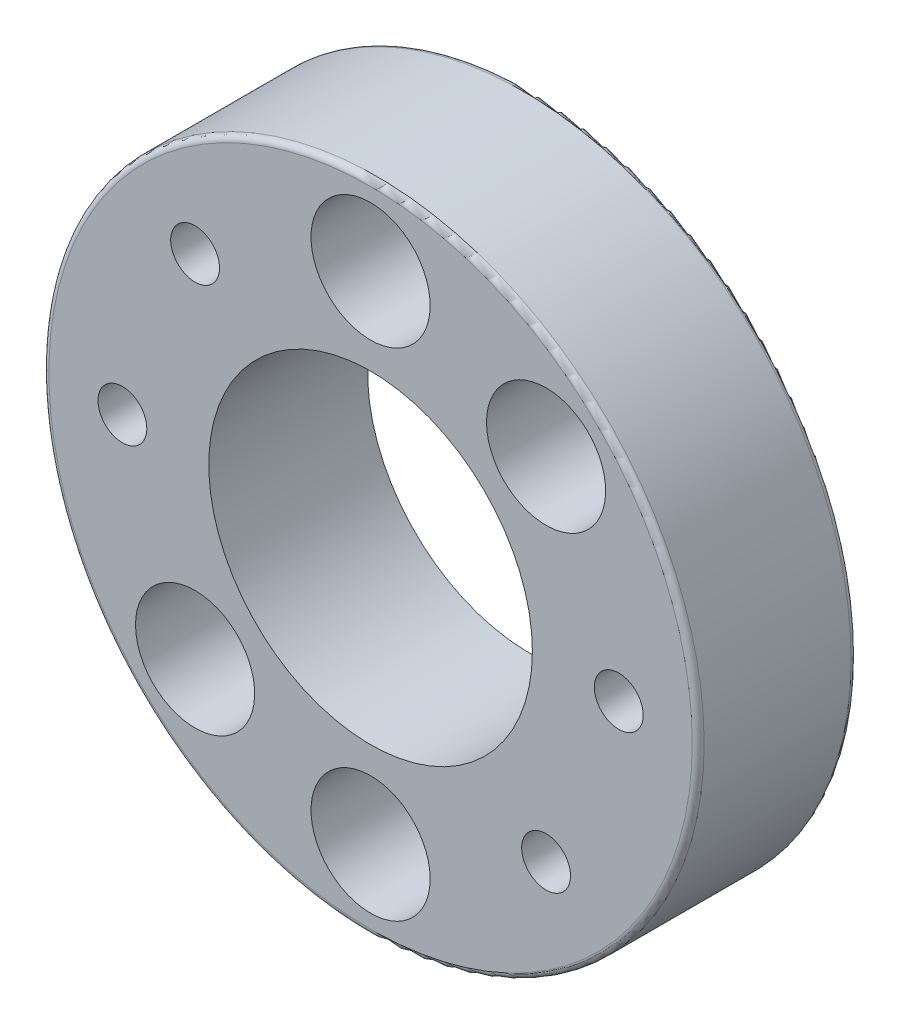
SolidWorks part; units mm, degrees
ref_plane "Front Plane" through (0, 0, 0) normal (0, 0, 1) x (1, 0, 0)
ref_plane "Top Plane" through (0, 0, 0) normal (0, 1, 0) x (1, 0, 0)
ref_plane "Right Plane" through (0, 0, 0) normal (1, 0, 0) x (0, 0, -1)
ref_axis "Axis_X" through (-6.6, 0, 0) along (1, 0, 0)
ref_axis "Axis_Y" through (0, 6.6, 0) along (0, -1, 0)
ref_axis "Axis_Z" through (0, 0, -0.15) along (0, 0, 1)
sketch "Sketch1" plane through (0, 0, 0) normal (0, 0, 1) x (1, 0, 0)
  circle A0 centre (0, 0) radius 16.5
  circle A1 centre (0, 0) radius 8.15
  dimension "D" = 33
  dimension "D3_s" = 16.3
extrude "Boss-Extrude1" add sketch "Sketch1" along normal blind 8
sketch "Sketch2" plane through (0, 0, 8) normal (0, 0, 1) x (1, 0, 0)
  line L0 (0, 0) -> (-8.15, 0) construction
  circle A0 centre (0, 12.5) radius 3
  circle A1 centre (0, -12.5) radius 3
  circle A2 centre (0, 0) radius 8.15 construction
  dimension "MSM_43" = 6
  dimension "MSM_8" = 25
extrude "Cut-Extrude1" cut sketch "Sketch2" against normal through all
hole_wizard "Tap1" positions "Sketch3" profile "Sketch4" hole size "M1.6x0.35" standard "JIS" end condition through all
sketch "Sketch3" plane through (0, 0, 8) normal (0, 0, 1) x (1, 0, 0)
  line L0 (0, 0) -> (0, 8.15) construction
  circle A0 centre (0, 0) radius 8.15 construction
  point P0 (-12.5, 0)
  point P2 (12.5, 0)
  dimension "MSM_8" = 25
sketch "Sketch4" plane through (-12.5, 0, 8) normal (1, 0, 0) x (0, -1, 0)
  line L0 (0, 0) -> (0, 8)
  line L1 (0, 8) -> (1.2295, 8)
  line L2 (1.2295, 8) -> (1.2295, 0)
  line L5 (1.2295, 0) -> (0, 0)
  line L11 (0, -6.35) -> (0, 107.95) construction
  dimension "HSD_11" = 2.459
  dimension "Thru Hole Depth" = 8
cosmetic thread "Thread1"
cosmetic thread "Thread2"
pattern_circular "CirPattern11" count 2 every 45 about axis through (0, 0, -0.15) along (0, 0, 1) of "Cut-Extrude1", "Tap1" reverse direction yes
fillet "Fillet1" radius 0.3 2 edges at (16.5, 0, 0) (16.5, 0, 8)
equation "\"Factor\"= 1.082532"
